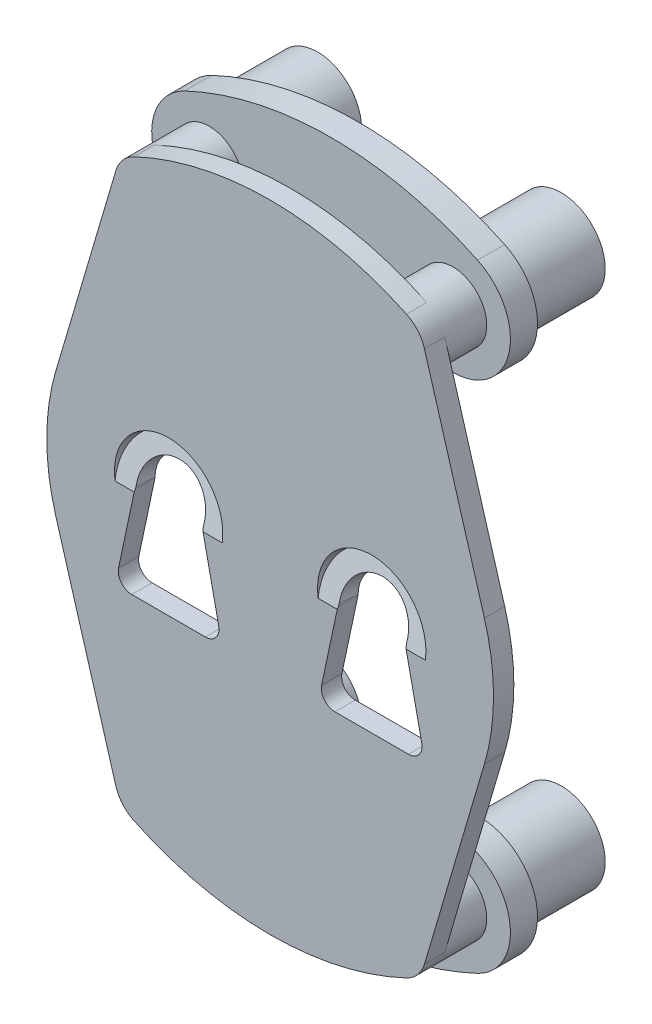
SolidWorks part; units mm, degrees
material "PET"
ref_plane "Front Plane" through (0, 0, 0) normal (0, 0, 1) x (1, 0, 0)
ref_plane "Top Plane" through (0, 0, 0) normal (0, 1, 0) x (1, 0, 0)
ref_plane "Right Plane" through (0, 0, 0) normal (1, 0, 0) x (0, 0, -1)
sketch "Sketch1" plane through (0, 0, 0) normal (0, 0, 1) x (1, 0, 0)
  line L0 (0, -1072.5) -> (0, -1056.336) construction
  line L1 (0, -1056.336) -> (0, -1072.5) construction
  line L2 (0, -1260) -> (125.8852, -1260) construction
  arc A0 (-108.2143, -1031.8643) -> (-48.3761, -1078.8481) centre (-90, -1070.2633) ccw
  circle A1 centre (0, -1260) radius 164.9997 construction
  arc A2 (108.2143, -1031.8643) -> (48.3761, -1078.8481) centre (90, -1070.2633) cw
  arc A3 (108.2143, -1488.1357) -> (48.3761, -1441.1519) centre (90, -1449.7367) ccw
  arc A4 (-108.2143, -1488.1357) -> (-48.3761, -1441.1519) centre (-90, -1449.7367) cw
  arc A5 (-48.3761, -1441.1519) -> (48.3761, -1441.1519) centre (0, -1260) ccw
  arc A6 (-108.2143, -1488.1357) -> (108.2143, -1488.1357) centre (0, -1260) ccw
  arc A7 (108.2143, -1031.8643) -> (-108.2143, -1031.8643) centre (0, -1260) ccw
  arc A8 (48.3761, -1078.8481) -> (-48.3761, -1078.8481) centre (0, -1260) ccw
  dimension "D1" = 85
  dimension "D2" = 375
extrude "Boss-Extrude1" add sketch "Sketch1" along normal blind 20
sketch "Sketch2" plane through (0, 0, 20) normal (0, 0, 1) x (1, 0, 0)
  line L0 (0, -1260) -> (0, -1081.2764) construction
  line L1 (0, -1260) -> (209.3364, -1260) construction
  circle A0 centre (90, -1070.2633) radius 25
  arc A1 (48.3761, -1078.8481) -> (108.2143, -1031.8643) centre (90, -1070.2633) ccw construction
  circle A2 centre (0, -1260) radius 164.9997 construction
  circle A3 centre (-90, -1070.2633) radius 25
  circle A4 centre (-90, -1449.7367) radius 25
  circle A5 centre (90, -1449.7367) radius 25
  point P8 (0, 0)
  dimension "D1" = 50
extrude "Boss-Extrude2" add sketch "Sketch2" along normal blind 30
sketch "Sketch3" plane through (0, 0, 50) normal (0, 0, 1) x (1, 0, 0)
  line L0 (0, -1260) -> (0, -1388.1592) construction
  line L1 (-113.9787, -1063.1908) -> (-158.2596, -1213.3214)
  line L2 (0, -1260) -> (72.7833, -1260) construction
  line L3 (113.9787, -1063.1908) -> (158.2596, -1213.3214)
  line L4 (-113.9787, -1456.8092) -> (-158.2596, -1306.6786)
  line L5 (113.9787, -1456.8092) -> (158.2596, -1306.6786)
  line L7 (-100, -1260) -> (-111.9863, -1316.3912)
  line L8 (-75, -1260) -> (-75, -1349.8105) construction
  line L9 (-50, -1260) -> (-38.0137, -1316.3912)
  line L10 (-102.2048, -1328.4703) -> (-47.7952, -1328.4703)
  line L11 (100, -1260) -> (111.9863, -1316.3912)
  line L12 (102.2048, -1328.4703) -> (47.7952, -1328.4703)
  line L13 (50, -1260) -> (38.0137, -1316.3912)
  arc A0 (-158.2596, -1213.3214) -> (-158.2596, -1306.6786) centre (0, -1260) ccw
  arc A1 (-50, -1260) -> (-100, -1260) centre (-75, -1260) ccw
  circle A2 centre (-90, -1070.2633) radius 25 construction
  arc A3 (-100.7143, -1472.3244) -> (100.7143, -1472.3244) centre (0, -1260) ccw
  arc A4 (-113.9787, -1063.1908) -> (-100.7143, -1047.6756) centre (-90, -1070.2633) cw
  arc A5 (113.9787, -1063.1908) -> (100.7143, -1047.6756) centre (90, -1070.2633) ccw
  arc A6 (-113.9787, -1456.8092) -> (-100.7143, -1472.3244) centre (-90, -1449.7367) ccw
  arc A7 (113.9787, -1456.8092) -> (100.7143, -1472.3244) centre (90, -1449.7367) cw
  arc A8 (100.7143, -1047.6756) -> (-100.7143, -1047.6756) centre (0, -1260) ccw
  arc A9 (158.2596, -1306.6786) -> (158.2596, -1213.3214) centre (0, -1260) ccw
  arc A11 (-38.0137, -1316.3912) -> (-47.7952, -1328.4703) centre (-47.7952, -1318.4703) cw
  arc A12 (-111.9863, -1316.3912) -> (-102.2048, -1328.4703) centre (-102.2048, -1318.4703) ccw
  arc A13 (50, -1260) -> (100, -1260) centre (75, -1260) cw
  arc A14 (111.9863, -1316.3912) -> (102.2048, -1328.4703) centre (102.2048, -1318.4703) cw
  arc A15 (38.0137, -1316.3912) -> (47.7952, -1328.4703) centre (47.7952, -1318.4703) ccw
  point P34 (-35.4462, -1328.4703)
  point P37 (-114.5538, -1328.4703)
  dimension "D1" = 330
  dimension "D2" = 50
  dimension "D6" = 10
  dimension "D3" = 75
  dimension "D4" = 70
  dimension "D5" = 12
extrude "Boss-Extrude3" add sketch "Sketch3" along normal blind 15
ref_axis "Axis1" through (75, -1235, 65) along (-1, 0, 0)
ref_plane "Plane1" through (0, -66.4793, -248.1042) normal (0, 0.2588, 0.9659) x (-1, 0, 0)
sketch "Sketch4" plane through (0, -66.4793, -248.1042) normal (0, 0.2588, 0.9659) x (-1, 0, 0)
  line L0 (-47.7952, 1300.027) -> (-102.2048, 1300.027) construction
  line L1 (-75, 1300.027) -> (75, 1300.027) construction
  line L2 (102.2048, 1300.027) -> (47.7952, 1300.027) construction
  line L3 (0, 1300.027) -> (0, 1241.7155) construction
  circle A0 centre (-75, 1230.027) radius 25
  circle A1 centre (75, 1230.027) radius 25
  point P5 (-75, 1300.027)
  dimension "D1" = 50
  dimension "D2" = 70
extrude "Cut-Extrude1" cut sketch "Sketch4" against normal blind 51 and the other way blind 40
ref_plane "Plane2" through (0, -61.3029, -228.7857) normal (0, 0.2588, 0.9659) x (-1, 0, 0)
sketch "Sketch5" plane through (0, -61.3029, -228.7857) normal (0, 0.2588, 0.9659) x (-1, 0, 0)
  line L0 (-75, 1300.027) -> (75, 1300.027) construction
  line L1 (-47.7952, 1300.027) -> (-102.2048, 1300.027) construction
  line L2 (102.2048, 1300.027) -> (47.7952, 1300.027) construction
  line L3 (0, 1300.027) -> (0, 1161.6421) construction
  circle A0 centre (-75, 1230.027) radius 40
  arc A1 (-99.9227, 1231.9919) -> (-50.0773, 1231.9919) centre (-75, 1230.027) ccw construction
  circle A2 centre (75, 1230.027) radius 40
  dimension "D1" = 80
extrude "Cut-Extrude2" cut sketch "Sketch5" against normal blind 27
sketch "Sketch6" plane through (0, 0, 0) normal (0, 0, -1) x (-1, 0, 0)
  line L0 (48.3761, -1078.8481) -> (-48.3761, -1078.8481) construction
  line L1 (0, -1078.8481) -> (0, -1030.4633) construction
  line L2 (165, -1260) -> (-165, -1260) construction
  circle A0 centre (90, -1070.2633) radius 32.5
  arc A1 (48.3761, -1078.8481) -> (108.2143, -1031.8643) centre (90, -1070.2633) ccw construction
  arc A2 (158.2596, -1306.6786) -> (158.2596, -1213.3214) centre (0, -1260) ccw construction
  arc A3 (-158.2596, -1213.3214) -> (-158.2596, -1306.6786) centre (0, -1260) ccw construction
  circle A4 centre (-90, -1070.2633) radius 32.5
  circle A5 centre (-90, -1449.7367) radius 32.5
  circle A6 centre (90, -1449.7367) radius 32.5
  point P20 (163.9679, -1241.574)
  point P21 (165, -1260)
  dimension "D1" = 65
extrude "Boss-Extrude4" add sketch "Sketch6" along normal up to surface (60 mm away)
